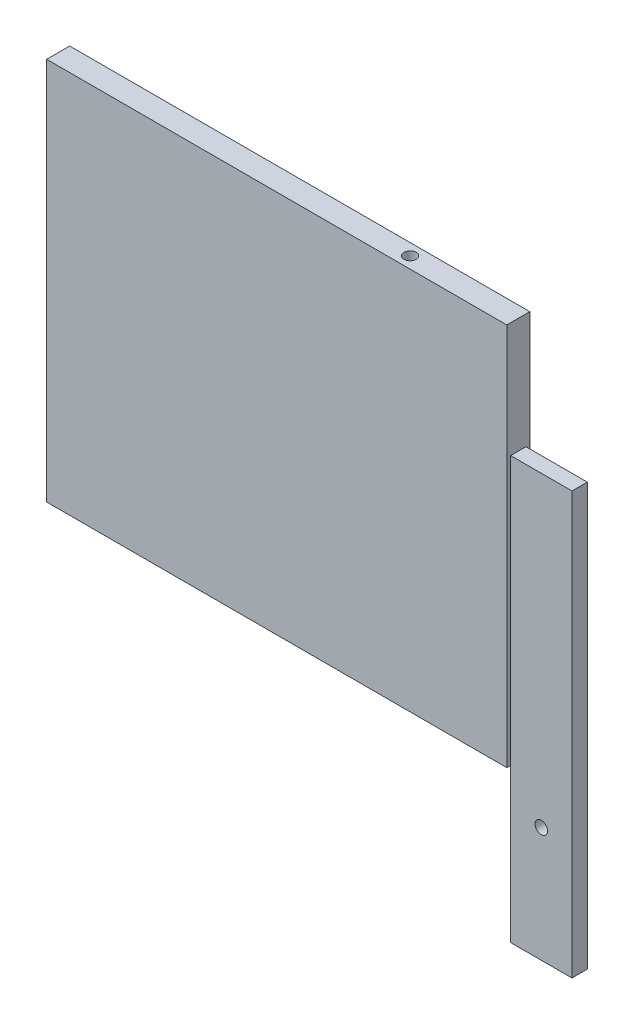
SolidWorks part; units mm, degrees
ref_plane "Front Plane" through (0, 0, 0) normal (0, 0, 1) x (1, 0, 0)
ref_plane "Top Plane" through (0, 0, 0) normal (0, 1, 0) x (1, 0, 0)
ref_plane "Right Plane" through (0, 0, 0) normal (1, 0, 0) x (0, 0, -1)
sketch "Sketch1" plane through (0, 0, 0) normal (0, 0, 1) x (1, 0, 0)
  line L1 (-26.749, 19.5473) -> (33.251, 19.5473)
  line L2 (-26.749, 19.5473) -> (-26.749, -30.4527)
  line L3 (-26.749, -30.4527) -> (33.251, -30.4527)
  line L4 (33.251, 19.5473) -> (33.251, -30.4527)
  dimension "D1" = 60
  dimension "D2" = 50
extrude "Boss-Extrude1" add sketch "Sketch1" along normal blind 3
sketch "Sketch6" plane through (33.251, 0, 0) normal (1, 0, 0) x (0, 0, -1)
  line L0 (-3, 19.5473) -> (0, 19.5473) construction
  line L1 (-2.5, 4.5473) -> (-0.5, 4.5473)
  line L2 (-2.5, 4.5473) -> (-2.5, -15.4527)
  line L3 (-2.5, -15.4527) -> (-0.5, -15.4527)
  line L4 (-0.5, 4.5473) -> (-0.5, -15.4527)
  line L5 (-3, -30.4527) -> (0, -30.4527) construction
  line L6 (0, -30.4527) -> (0, 19.5473) construction
  line L7 (-3, -30.4527) -> (-3, 19.5473) construction
  dimension "D1" = 15
  dimension "D2" = 15
  dimension "D3" = 0.5
  dimension "D4" = 0.5
extrude "Boss-Extrude4" add sketch "Sketch6" along normal blind 8
sketch "Sketch7" plane through (0, -15.4527, 0) normal (0, -1, 0) x (1, 0, 0)
  circle A0 centre (19.1457, 1.5) radius 0.7944
extrude "Cut-Extrude1" cut sketch "Sketch7" against normal up to next
sketch "Sketch8" plane through (0, -15.4527, 0) normal (0, -1, 0) x (1, 0, 0)
  line L1 (33.251, 2.5) -> (41.251, 2.5)
  line L2 (33.251, 2.5) -> (33.251, 0.5)
  line L3 (33.251, 0.5) -> (41.251, 0.5)
  line L4 (41.251, 2.5) -> (41.251, 0.5)
extrude "Boss-Extrude5" add sketch "Sketch8" along normal blind 35
sketch "Sketch9" plane through (0, 0, 0.5) normal (0, 0, -1) x (-1, 0, 0)
  line L0 (-37.251, 4.5473) -> (-37.251, -50.4527) construction
  line L1 (-41.251, 4.5473) -> (-33.251, 4.5473) construction
  line L2 (-33.251, -50.4527) -> (-41.251, -50.4527) construction
  line L3 (26.749, -30.4527) -> (-33.251, -30.4527) construction
  circle A0 centre (-37.251, -35.4527) radius 0.815
  point P8 (0, 0)
  point P9 (0, 0)
  point P12 (0, 0)
  dimension "D1" = 1.63
  dimension "D2" = 5
extrude "Cut-Extrude2" cut sketch "Sketch9" against normal through all
